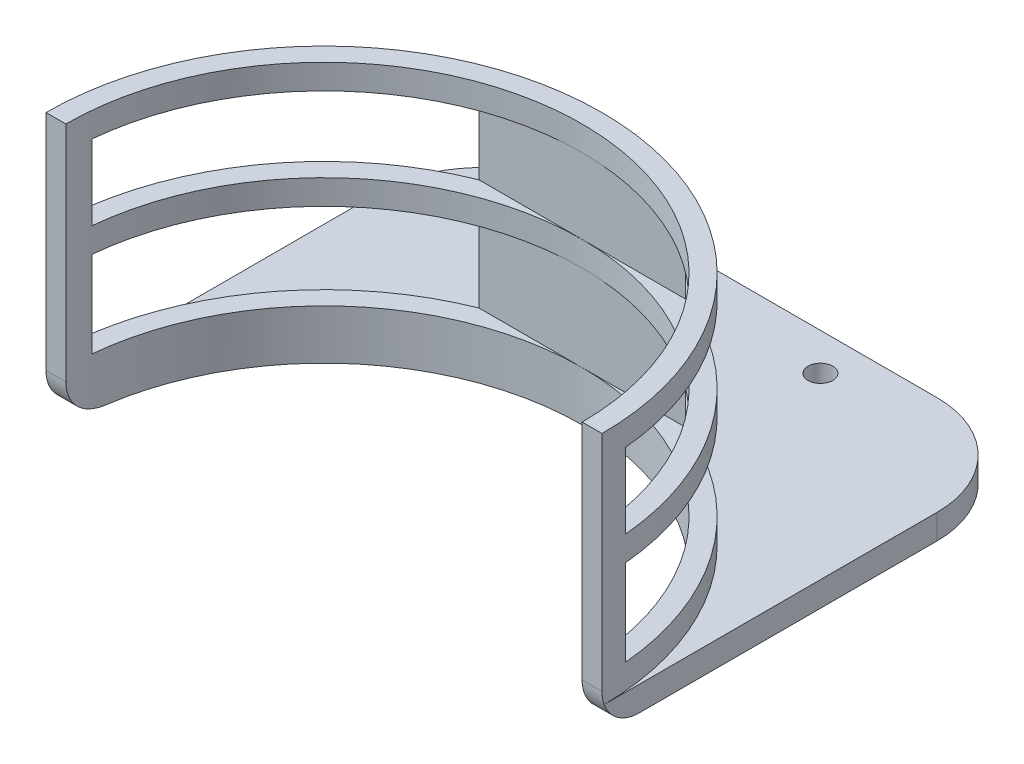
SolidWorks part; units mm, degrees
ref_plane "Front Plane" through (0, 0, 0) normal (0, 0, 1) x (1, 0, 0)
ref_plane "Top Plane" through (0, 0, 0) normal (0, 1, 0) x (1, 0, 0)
ref_plane "Right Plane" through (0, 0, 0) normal (1, 0, 0) x (0, 0, -1)
sketch "Sketch1" plane through (0, 0, 0) normal (0, 1, 0) x (1, 0, 0)
  line L0 (-22.4, 0) -> (-20.8, 0)
  line L1 (20.8, 0) -> (22.4, 0)
  arc A0 (20.8, 0) -> (-20.8, 0) centre (0, 0) ccw
  arc A1 (22.4, 0) -> (-22.4, 0) centre (0, 0) ccw
  dimension "D1" = 41.6
  dimension "D2" = 44.8
extrude "Boss-Extrude1" add sketch "Sketch1" along normal blind 19
sketch "Sketch2" plane through (0, 0, 0) normal (0, -1, 0) x (1, 0, 0)
  line L1 (-22.4, 0) -> (22.4, 0)
  line L2 (-22.4, 0) -> (-22.4, -35)
  line L3 (-22.4, -35) -> (22.4, -35)
  line L4 (22.4, 0) -> (22.4, -35)
  point P5 (21.5165, 0)
  dimension "D1" = 35
extrude "Boss-Extrude2" add sketch "Sketch2" along normal blind 2
sketch "Sketch3" plane through (0, 0, 0) normal (0, 1, 0) x (1, 0, 0)
  circle A0 centre (0, 0) radius 20.8
extrude "Cut-Extrude1" cut sketch "Sketch3" against normal blind 2
sketch "Sketch4" plane through (0, 0, 0) normal (0, 1, 0) x (1, 0, 0)
  line L0 (0, 35) -> (0, 22.4) construction
  line L1 (-22.4, 35) -> (22.4, 35) construction
  line L2 (-22.4, 29.05) -> (22.4, 29.05) construction
  line L3 (-22.4, 0) -> (-22.4, 35) construction
  line L4 (22.4, 35) -> (22.4, 0) construction
  line L5 (20.8, 0) -> (22.4, 0) construction
  circle A0 centre (-8, 32) radius 1
  arc A1 (22.4, 0) -> (-22.4, 0) centre (0, 0) ccw construction
  circle A2 centre (8, 32) radius 1
  point P17 (-40.4253, 28.1991)
  dimension "D1" = 2
  dimension "D4" = 8
  dimension "D2" = 3
  dimension "D3" = 29.05
extrude "Cut-Extrude2" cut sketch "Sketch4" against normal blind 2
fillet "Fillet1" radius 8 2 edges at (22.4, -1, -35) (-22.4, -1, -35)
sketch "Sketch5" plane through (-22.4, 0, 0) normal (-1, 0, 0) x (0, 0, 1)
  line L1 (0, 0) -> (-22.4, 0) construction
  line L2 (0, 0) -> (0, 19) construction
  line L3 (0, 19) -> (-22.4, 19) construction
  line L4 (-22.4, 0) -> (-22.4, 19) construction
  line L5 (-22.4, 19) -> (-22.4, 0) construction
  line L6 (-20.8, 17) -> (-2, 17)
  line L7 (-20.8, 17) -> (-20.8, 10.9449)
  line L8 (-20.8, 10.9449) -> (-2, 10.9449)
  line L9 (-2, 17) -> (-2, 10.9449)
  line L10 (-20.8, 8.9449) -> (-2, 8.9449)
  line L11 (-20.8, 8.9449) -> (-20.8, 2)
  line L12 (-20.8, 2) -> (-2, 2)
  line L13 (-2, 8.9449) -> (-2, 2)
  dimension "D1" = 2
  dimension "D2" = 2
  dimension "D3" = 2
  dimension "D4" = 1.6
  dimension "D5" = 2
extrude "Cut-Extrude3" cut sketch "Sketch5" against normal blind 47
fillet "Fillet2" radius 3 2 edges at (-21.6, -2, 0) (21.6, -2, 0)
